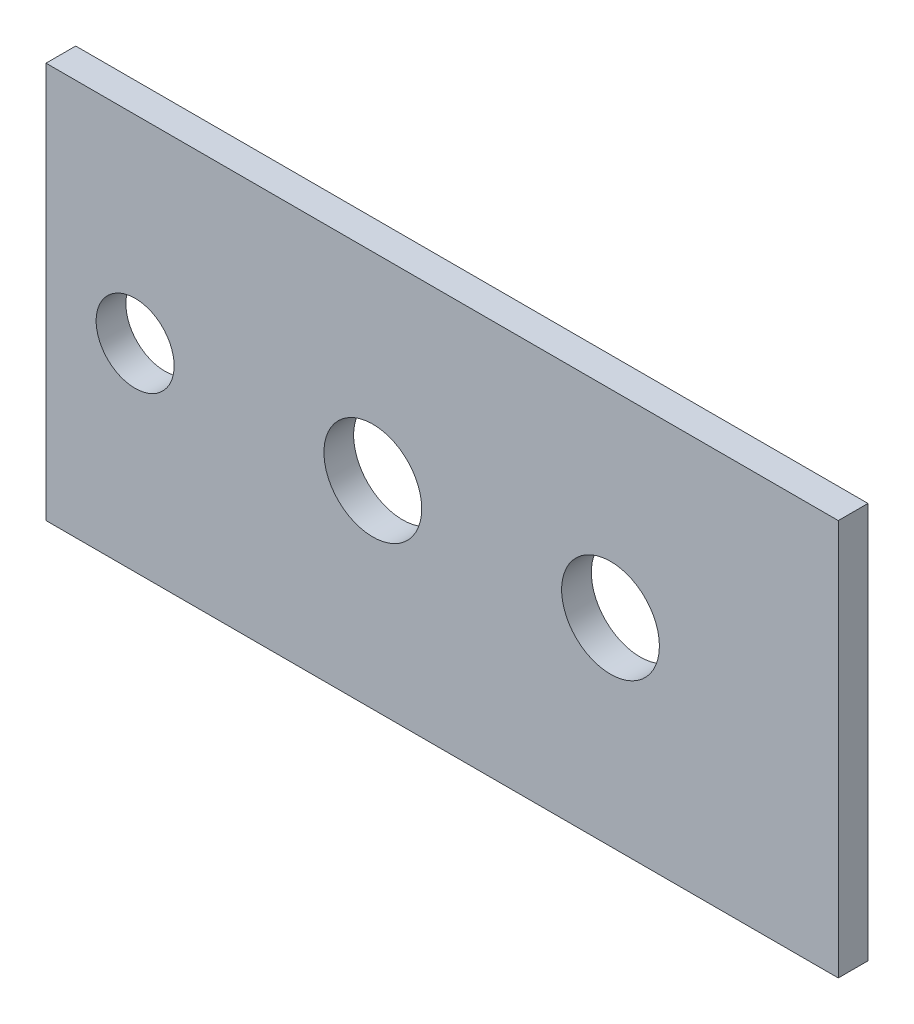
SolidWorks part; units mm, degrees
ref_plane "Front Plane" through (0, 0, 0) normal (0, 0, 1) x (1, 0, 0)
ref_plane "Top Plane" through (0, 0, 0) normal (0, 1, 0) x (1, 0, 0)
ref_plane "Right Plane" through (0, 0, 0) normal (1, 0, 0) x (0, 0, -1)
sketch "Sketch1" plane through (0, 0, 0) normal (0, 0, 1) x (1, 0, 0)
  line L1 (0, 0) -> (80, 0)
  line L2 (0, 0) -> (0, 40)
  line L3 (0, 40) -> (80, 40)
  line L4 (80, 0) -> (80, 40)
  dimension "D1" = 80
  dimension "D2" = 40
extrude "Boss-Extrude1" add sketch "Sketch1" along normal blind 3 contours L3 L4 L1 L2
sketch "Sketch2" plane through (0, 0, 3) normal (0, 0, 1) x (1, 0, 0)
  line L0 (0, 20) -> (80, 20) construction
  line L1 (0, 0) -> (0, 40) construction
  line L2 (80, 0) -> (80, 40) construction
  circle A0 centre (9, 20) radius 3.9365
  circle A1 centre (33, 20) radius 4.9365
  circle A2 centre (57, 20) radius 4.9365
  dimension "D1" = 7.873
  dimension "D2" = 9.873
  dimension "D3" = 9.873
  dimension "D4" = 9
  dimension "D5" = 24
  dimension "D6" = 24
extrude "Cut-Extrude1" cut sketch "Sketch2" against normal through all contours A1 L0 | L0 A1 | A2 L0 | L0 A2 | A0 region at (57, 22.0951, 3) region at (57, 17.9049, 3) region at (33, 22.0951, 3) region at (33, 17.9049, 3)
ref_axis "Axis1" through (9, 20, 0) along (0, 0, 1)
